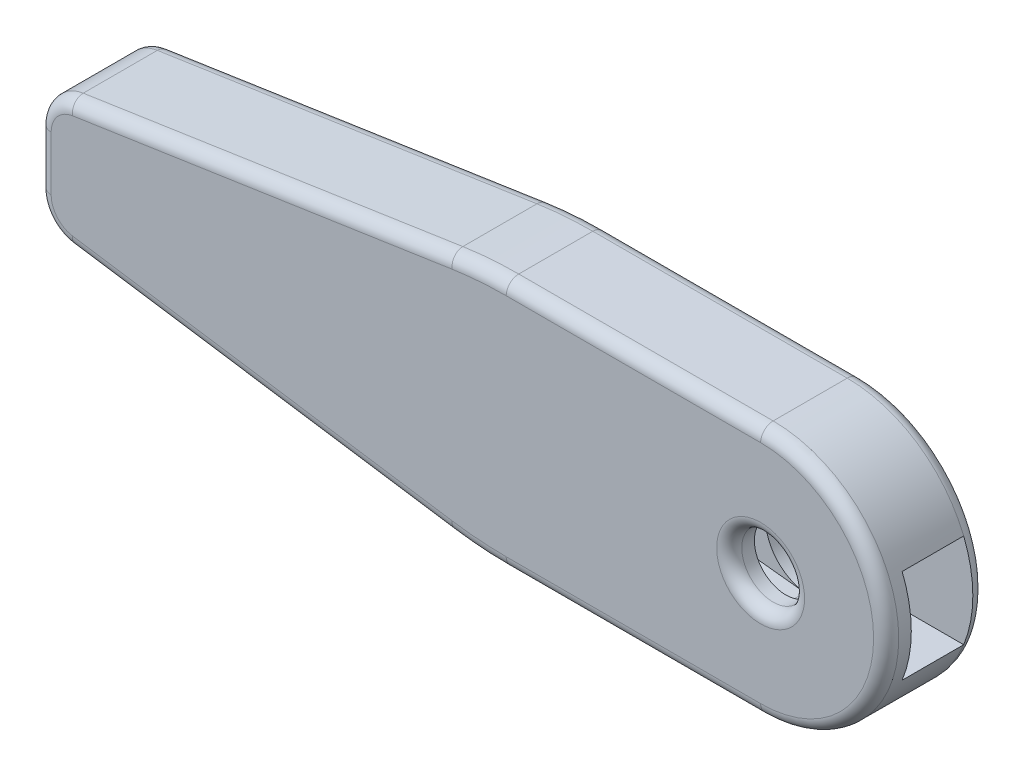
SolidWorks part; units mm, degrees
material "Alliage 1060"
ref_plane "Plan de dessus" through (0, 0, 0) normal (0, 0, 1) x (1, 0, 0)
ref_plane "Plan de droite" through (0, 0, 0) normal (0, 1, 0) x (1, 0, 0)
ref_plane "Plan de face" through (0, 0, 0) normal (1, 0, 0) x (0, 0, -1)
sketch "Esquisse1" plane through (0, 0, 0) normal (0, 0, 1) x (1, 0, 0)
  line L29 (44.7375, 10) -> (65, 10)
  line L30 (65, -10) -> (44.7375, -10)
  line L31 (7.5, 0) -> (42.5, 0) construction
  line L32 (42.5, 21.6245) -> (42.5, -21.6245) construction
  line L34 (10.055, 5.1332) -> (40.2873, 9.6681)
  line L35 (10.055, -5.1332) -> (40.2873, -9.6681)
  line L37 (7.5, 2.1664) -> (7.5, -2.1664)
  arc A5 (65, -10) -> (65, 10) centre (65, 0) ccw
  arc A19 (44.7375, 10) -> (40.2873, 9.6681) centre (44.7375, -20) ccw
  arc A20 (44.7375, -10) -> (40.2873, -9.6681) centre (44.7375, 20) cw
  arc A21 (10.055, -5.1332) -> (7.5, -2.1664) centre (10.5, -2.1664) cw
  arc A22 (10.055, 5.1332) -> (7.5, 2.1664) centre (10.5, 2.1664) ccw
  point P18 (42.5, 10)
  point P22 (42.5, -10)
  dimension "D1" = 3
  dimension "D3" = 10
  dimension "D4" = 30
extrude "Boss.-Extru.2" add sketch "Esquisse1" along normal blind 10.4
sketch "Esquisse2" plane through (0, 0, 10.4) normal (0, 0, 1) x (1, 0, 0)
  circle A0 centre (65, 0) radius 2.5
  dimension "D1" = 5
  dimension "D2" = 65
extrude "Enlèv. mat.-Extru.1" cut sketch "Esquisse2" against normal blind 2.5
ref_plane "Plan1" through (0, 0, 5.9) normal (0, 0, 1) x (1, 0, 0)
sketch "Esquisse3" plane through (0, 0, 5.9) normal (0, 0, 1) x (1, 0, 0)
  line L1 (87.5, 3.75) -> (87.5, -3.75)
  line L2 (65, 3.5) -> (65, 3.75)
  line L3 (65, 3.75) -> (87.5, 3.75)
  line L5 (87.5, -3.75) -> (65, -3.75)
  line L6 (65, -3.75) -> (65, -3.5)
  line L7 (50.7857, 1.9885) -> (64.625, 3.4799)
  line L8 (50.7857, -1.9885) -> (64.625, -3.4799)
  arc A1 (64.625, -3.4799) -> (65, -3.5) centre (65, 0) ccw
  arc A2 (50.7857, 1.9885) -> (50.7857, -1.9885) centre (51, 0) ccw
  arc A3 (65, 3.5) -> (64.625, 3.4799) centre (65, 0) ccw
  dimension "D1" = 65
  dimension "D3" = 7
  dimension "D4" = 4
  dimension "D5" = 22.5
  dimension "D6" = 7.5
  dimension "D7" = 0.25
  dimension "D8" = 50.7857
  dimension "D9" = 64.625
  dimension "D11" = 3.75
  dimension "D12" = 65
  dimension "D13" = 3.75
extrude "Enlèv. mat.-Extru.2" cut sketch "Esquisse3" against normal blind 1.9
ref_plane "Plan2" through (0, 0, 4) normal (0, 0, 1) x (1, 0, 0)
sketch "Esquisse4" plane through (0, 0, 4) normal (0, 0, 1) x (1, 0, 0)
  line L0 (65, 3.5) -> (65, 3.75)
  line L1 (65, 3.75) -> (88.0776, 3.75)
  line L2 (65, -3.75) -> (88.0776, -3.75)
  line L3 (88.0776, 3.75) -> (88.0776, -3.75)
  line L4 (65, -3.5) -> (65, -3.75)
  arc A0 (65, 3.5) -> (65, -3.5) centre (65, 0) ccw
  dimension "D1" = 7
  dimension "D2" = 23.0776
  dimension "D3" = 7.5
  dimension "D4" = 65
  dimension "D5" = 3.75
  dimension "D6" = 0.25
extrude "Enlèv. mat.-Extru.3" cut sketch "Esquisse4" against normal blind 3
ref_plane "Plan3" through (0, 0, 1) normal (0, 0, 1) x (1, 0, 0)
sketch "Esquisse6" plane through (0, 0, 1) normal (0, 0, 1) x (1, 0, 0)
  circle A0 centre (65, 0) radius 2.625
  dimension "D1" = 5.25
  dimension "D2" = 65
extrude "Enlèv. mat.-Extru.4" cut sketch "Esquisse6" against normal through all
sketch "Esquisse8" plane through (0, 0, 0) normal (1, 0, 0) x (0, 0, -1)
  line L2 (-7.9, 12.5305) -> (-7.9, -11.3569)
  line L3 (-7.9, -11.3569) -> (-11.9911, -11.3569)
  line L4 (-11.9911, -11.3569) -> (-11.9911, 12.5305)
  line L5 (-11.9911, 12.5305) -> (-7.9, 12.5305)
extrude "Enlèv. mat.-Extru.5" cut sketch "Esquisse8" along normal blind 79
sketch "Esquisse9" plane through (0, 0, 7.9) normal (0, 0, 1) x (1, 0, 0)
  circle A0 centre (65, 0) radius 2.5
  dimension "D1" = 5
extrude "Enlèv. mat.-Extru.6" cut sketch "Esquisse9" against normal up to next
fillet "Congé2" radius 1 11 edges at (25.1711, 7.4007, 7.9) (42.5062, 9.9169, 7.9) (54.8687, 10, 7.9) (75, 0, 7.9) (54.8687, -10, 7.9) (42.5062, -9.9169, 7.9) (25.1711, -7.4007, 7.9) (67.5, 0, 7.9) (8.2268, -4.1241, 7.9) (7.5, 0, 7.9) (8.2268, 4.1241, 7.9)
fillet "Congé3" radius 1 11 edges at (25.1711, -7.4007, 0) (42.5062, -9.9169, 0) (54.8687, -10, 0) (75, 0, 0) (54.8687, 10, 0) (42.5062, 9.9169, 0) (25.1711, 7.4007, 0) (8.2268, 4.1241, 0) (7.5, 0, 0) (8.2268, -4.1241, 0) (67.625, 0, 0)
equation "\"è\"=2.69927"
